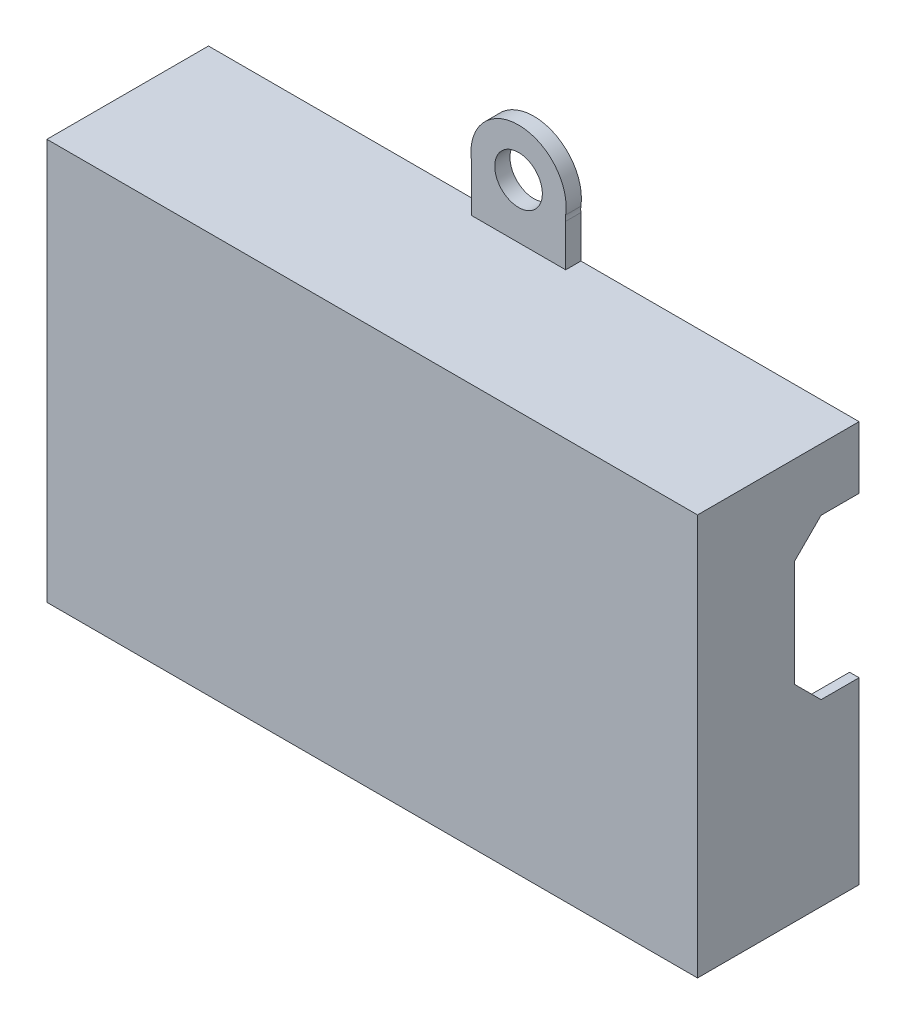
SolidWorks part; units mm, degrees
ref_plane "Front Plane" through (0, 0, 0) normal (0, 0, 1) x (1, 0, 0)
ref_plane "Top Plane" through (0, 0, 0) normal (0, 1, 0) x (1, 0, 0)
ref_plane "Right Plane" through (0, 0, 0) normal (1, 0, 0) x (0, 0, -1)
sketch "Sketch1" plane through (0, 0, 0) normal (0, 0, 1) x (1, 0, 0)
  line L0 (-16.375, 9.825) -> (16.375, -9.825) construction
  line L1 (-16.375, -9.825) -> (-16.575, -9.825) construction
  line L2 (16.575, 10.025) -> (-16.575, 10.025)
  line L3 (16.575, 10.025) -> (16.575, -10.025)
  line L4 (-16.375, 9.825) -> (-16.375, -9.825)
  line L5 (-16.375, -9.825) -> (16.375, -9.825)
  line L6 (16.375, -9.825) -> (16.375, 9.825)
  line L7 (16.375, 9.825) -> (-16.375, 9.825)
  line L8 (-16.375, 9.825) -> (-16.375, -9.825)
  line L9 (-16.375, -9.825) -> (16.375, -9.825)
  line L10 (16.375, -9.825) -> (16.375, 9.825)
  line L11 (16.375, 9.825) -> (-16.375, 9.825)
  line L12 (16.575, -10.025) -> (-16.575, -10.025)
  line L13 (-16.575, 10.025) -> (-16.575, -10.025)
  line L14 (16.575, 10.025) -> (-16.575, -10.025) construction
  line L15 (-13.9701, -11.875) -> (-3.4641, -11.875)
  line L18 (3.4641, -11.875) -> (13.9701, -11.875)
  line L19 (14.8161, -12.3418) -> (24.6724, -27.981)
  line L20 (31.4404, -23.7156) -> (19.404, -4.6171)
  line L21 (19.25, -4.084) -> (19.25, 4.084)
  line L22 (19.404, 4.6171) -> (31.4404, 23.7156)
  line L23 (24.6724, 27.981) -> (14.8161, 12.3418)
  line L24 (13.9701, 11.875) -> (3.4641, 11.875)
  line L25 (-3.4641, 11.875) -> (-13.9701, 11.875)
  line L26 (-14.8161, 12.3418) -> (-24.6724, 27.981)
  line L27 (-31.4404, 23.7156) -> (-19.404, 4.6171)
  line L28 (-19.25, 4.084) -> (-19.25, 3.4641)
  line L29 (-19.25, -3.4641) -> (-19.25, -4.084)
  line L30 (-19.404, -4.6171) -> (-31.4404, -23.7156)
  line L31 (-24.6724, -27.981) -> (-14.8161, -12.3418)
  line L32 (-13.9701, -11.875) -> (-3.4641, -11.875)
  line L33 (3.4641, -11.875) -> (13.9701, -11.875)
  line L34 (14.8161, -12.3418) -> (24.6724, -27.981)
  line L35 (31.4404, -23.7156) -> (19.404, -4.6171)
  line L36 (19.25, -4.084) -> (19.25, 4.084)
  line L37 (19.404, 4.6171) -> (31.4404, 23.7156)
  line L38 (24.6724, 27.981) -> (14.8161, 12.3418)
  line L39 (13.9701, 11.875) -> (3.4641, 11.875)
  line L40 (-3.4641, 11.875) -> (-13.9701, 11.875)
  line L41 (-14.8161, 12.3418) -> (-24.6724, 27.981)
  line L42 (-31.4404, 23.7156) -> (-19.404, 4.6171)
  line L43 (-19.25, 4.084) -> (-19.25, 3.4641)
  line L44 (-19.25, -3.4641) -> (-19.25, -4.084)
  line L45 (-19.404, -4.6171) -> (-31.4404, -23.7156)
  line L46 (-24.6724, -27.981) -> (-14.8161, -12.3418)
  line L47 (16.575, -10.025) -> (-16.575, 10.025) construction
  line L48 (-16.375, -9.825) -> (-16.375, -10.025) construction
  line L49 (-16.575, -10.025) -> (-17.075, -10.025) construction
  line L50 (17.075, 10.525) -> (-17.075, 10.525)
  line L51 (17.075, 10.525) -> (17.075, -10.525)
  line L52 (17.075, -10.525) -> (-17.075, -10.525)
  line L53 (-17.075, 10.525) -> (-17.075, -10.525)
  line L54 (17.075, 10.525) -> (-17.075, -10.525) construction
  line L55 (17.075, -10.525) -> (-17.075, 10.525) construction
  line L56 (-16.575, -10.025) -> (-16.575, -10.525) construction
  line L57 (-20.3929, -2.4744) -> (-17.075, -2.4744)
  line L58 (-20.3929, 2.4744) -> (-17.075, 2.4744)
  line L59 (-2.4744, -13.0179) -> (-2.4744, -10.525)
  line L60 (2.4744, -13.0179) -> (2.4744, -10.525)
  line L61 (-2.4744, 13.0179) -> (-2.4744, 10.525)
  line L62 (2.4744, 13.0179) -> (2.4744, 10.525)
  circle A0 centre (0, -13.375) radius 1.25
  circle A1 centre (-20.75, 0) radius 1.25
  circle A2 centre (0, 13.375) radius 1.25
  arc A32 (-2.4744, -13.0179) -> (-3.4641, -11.875) centre (-3.4641, -12.875) ccw
  arc A33 (-2.4744, -13.0179) -> (2.4744, -13.0179) centre (0, -13.375) ccw
  arc A34 (3.4641, -11.875) -> (2.4744, -13.0179) centre (3.4641, -12.875) ccw
  arc A35 (14.8161, -12.3418) -> (13.9701, -11.875) centre (13.9701, -12.875) ccw
  arc A36 (24.7505, -28.8963) -> (24.6724, -27.981) centre (23.8264, -28.5142) ccw
  arc A37 (24.7505, -28.8963) -> (32.2325, -24.1809) centre (31.8198, -31.8198) ccw
  arc A38 (31.4404, -23.7156) -> (32.2325, -24.1809) centre (32.2864, -23.1824) ccw
  arc A39 (19.25, -4.084) -> (19.404, -4.6171) centre (20.25, -4.084) ccw
  arc A40 (19.404, 4.6171) -> (19.25, 4.084) centre (20.25, 4.084) ccw
  arc A41 (32.2325, 24.1809) -> (31.4404, 23.7156) centre (32.2864, 23.1824) ccw
  arc A42 (32.2325, 24.1809) -> (24.7505, 28.8963) centre (31.8198, 31.8198) ccw
  arc A43 (24.6724, 27.981) -> (24.7505, 28.8963) centre (23.8264, 28.5142) ccw
  arc A44 (13.9701, 11.875) -> (14.8161, 12.3418) centre (13.9701, 12.875) ccw
  arc A45 (2.4744, 13.0179) -> (3.4641, 11.875) centre (3.4641, 12.875) ccw
  arc A46 (2.4744, 13.0179) -> (-2.4744, 13.0179) centre (0, 13.375) ccw
  arc A47 (-3.4641, 11.875) -> (-2.4744, 13.0179) centre (-3.4641, 12.875) ccw
  arc A48 (-14.8161, 12.3418) -> (-13.9701, 11.875) centre (-13.9701, 12.875) ccw
  arc A49 (-24.7505, 28.8963) -> (-24.6724, 27.981) centre (-23.8264, 28.5142) ccw
  arc A50 (-24.7505, 28.8963) -> (-32.2325, 24.1809) centre (-31.8198, 31.8198) ccw
  arc A51 (-31.4404, 23.7156) -> (-32.2325, 24.1809) centre (-32.2864, 23.1824) ccw
  arc A52 (-19.25, 4.084) -> (-19.404, 4.6171) centre (-20.25, 4.084) ccw
  arc A53 (-20.3929, 2.4744) -> (-19.25, 3.4641) centre (-20.25, 3.4641) ccw
  arc A54 (-20.3929, 2.4744) -> (-20.3929, -2.4744) centre (-20.75, 0) ccw
  arc A55 (-19.25, -3.4641) -> (-20.3929, -2.4744) centre (-20.25, -3.4641) ccw
  arc A56 (-19.404, -4.6171) -> (-19.25, -4.084) centre (-20.25, -4.084) ccw
  arc A57 (-32.2325, -24.1809) -> (-31.4404, -23.7156) centre (-32.2864, -23.1824) ccw
  arc A58 (-32.2325, -24.1809) -> (-24.7505, -28.8963) centre (-31.8198, -31.8198) ccw
  arc A59 (-24.6724, -27.981) -> (-24.7505, -28.8963) centre (-23.8264, -28.5142) ccw
  arc A60 (-13.9701, -11.875) -> (-14.8161, -12.3418) centre (-13.9701, -12.875) ccw
  arc A61 (-2.4744, -13.0179) -> (-3.4641, -11.875) centre (-3.4641, -12.875) ccw
  arc A62 (-2.4744, -13.0179) -> (2.4744, -13.0179) centre (0, -13.375) ccw
  arc A63 (3.4641, -11.875) -> (2.4744, -13.0179) centre (3.4641, -12.875) ccw
  arc A64 (14.8161, -12.3418) -> (13.9701, -11.875) centre (13.9701, -12.875) ccw
  arc A65 (24.7505, -28.8963) -> (24.6724, -27.981) centre (23.8264, -28.5142) ccw
  arc A66 (24.7505, -28.8963) -> (32.2325, -24.1809) centre (31.8198, -31.8198) ccw
  arc A67 (31.4404, -23.7156) -> (32.2325, -24.1809) centre (32.2864, -23.1824) ccw
  arc A68 (19.25, -4.084) -> (19.404, -4.6171) centre (20.25, -4.084) ccw
  arc A69 (19.404, 4.6171) -> (19.25, 4.084) centre (20.25, 4.084) ccw
  arc A70 (32.2325, 24.1809) -> (31.4404, 23.7156) centre (32.2864, 23.1824) ccw
  arc A71 (32.2325, 24.1809) -> (24.7505, 28.8963) centre (31.8198, 31.8198) ccw
  arc A72 (24.6724, 27.981) -> (24.7505, 28.8963) centre (23.8264, 28.5142) ccw
  arc A73 (13.9701, 11.875) -> (14.8161, 12.3418) centre (13.9701, 12.875) ccw
  arc A74 (2.4744, 13.0179) -> (3.4641, 11.875) centre (3.4641, 12.875) ccw
  arc A75 (2.4744, 13.0179) -> (-2.4744, 13.0179) centre (0, 13.375) ccw
  arc A76 (-3.4641, 11.875) -> (-2.4744, 13.0179) centre (-3.4641, 12.875) ccw
  arc A77 (-14.8161, 12.3418) -> (-13.9701, 11.875) centre (-13.9701, 12.875) ccw
  arc A78 (-24.7505, 28.8963) -> (-24.6724, 27.981) centre (-23.8264, 28.5142) ccw
  arc A79 (-24.7505, 28.8963) -> (-32.2325, 24.1809) centre (-31.8198, 31.8198) ccw
  arc A80 (-31.4404, 23.7156) -> (-32.2325, 24.1809) centre (-32.2864, 23.1824) ccw
  arc A81 (-19.25, 4.084) -> (-19.404, 4.6171) centre (-20.25, 4.084) ccw
  arc A82 (-20.3929, 2.4744) -> (-19.25, 3.4641) centre (-20.25, 3.4641) ccw
  arc A83 (-20.3929, 2.4744) -> (-20.3929, -2.4744) centre (-20.75, 0) ccw
  arc A84 (-19.25, -3.4641) -> (-20.3929, -2.4744) centre (-20.25, -3.4641) ccw
  arc A85 (-19.404, -4.6171) -> (-19.25, -4.084) centre (-20.25, -4.084) ccw
  arc A86 (-32.2325, -24.1809) -> (-31.4404, -23.7156) centre (-32.2864, -23.1824) ccw
  arc A87 (-32.2325, -24.1809) -> (-24.7505, -28.8963) centre (-31.8198, -31.8198) ccw
  arc A88 (-24.6724, -27.981) -> (-24.7505, -28.8963) centre (-23.8264, -28.5142) ccw
  arc A89 (-13.9701, -11.875) -> (-14.8161, -12.3418) centre (-13.9701, -12.875) ccw
  point P6 (0, 0)
  point P25 (0, 0)
  dimension "D4" = 0.5
  dimension "D5" = 2.5
  dimension "D1" = 0
  dimension "D2" = 0
  dimension "D3" = 0.2
extrude "Boss-Extrude1" add sketch "Sketch1" along normal offset from surface (7.98 mm away) 2.5 contours A84 L57 L53 L58 A82 A83 | L50 L53 L52 L51 L13 L2 L3 L12 | A63 L60 L52 L59 A61 A62 | A76 L61 L50 L62 A74 A75 region at (-2.4011, -11.6286, 0) region at (-9.7747, -10.1238, 0) region at (-18.5911, -2.3949, 0) region at (0, 10.5982, 0) offset beyond the face yes
sketch "Sketch2" plane through (0, 0, 7.98) normal (0, 0, 1) x (1, 0, 0)
  line L0 (-2.5, 10.525) -> (2.4744, 10.525)
  line L1 (-17.075, 2.5) -> (-17.075, -2.5)
  line L2 (-2.5, -10.525) -> (2.4744, -10.525)
  line L6 (-20.1071, -2.4744) -> (-17.075, -2.4744)
  line L7 (-20.1071, -2.4744) -> (-17.075, -2.4744)
  line L8 (-17.075, -2.4744) -> (-17.075, -10.525)
  line L9 (-17.075, -2.4744) -> (-17.075, -10.525)
  line L20 (-17.075, -10.525) -> (-2.4744, -10.525)
  line L21 (-17.075, -10.525) -> (-2.4744, -10.525)
  line L22 (-2.4744, -10.525) -> (-2.4744, -12.7321)
  line L23 (-2.4744, -10.525) -> (-2.4744, -12.7321)
  line L24 (2.4744, -12.7321) -> (2.4744, -10.525)
  line L25 (2.4744, -12.7321) -> (2.4744, -10.525)
  line L26 (2.4744, -10.525) -> (17.075, -10.525)
  line L27 (2.4744, -10.525) -> (17.075, -10.525)
  line L28 (17.075, -10.525) -> (17.075, 10.525)
  line L29 (17.075, -10.525) -> (17.075, 10.525)
  line L30 (17.075, 10.525) -> (2.4744, 10.525)
  line L31 (17.075, 10.525) -> (2.4744, 10.525)
  line L32 (2.4744, 10.525) -> (2.4744, 12.7321)
  line L33 (2.4744, 10.525) -> (2.4744, 12.7321)
  line L34 (-2.4744, 12.7321) -> (-2.4744, 10.525)
  line L35 (-2.4744, 12.7321) -> (-2.4744, 10.525)
  line L36 (-2.4744, 10.525) -> (-17.075, 10.525)
  line L37 (-2.4744, 10.525) -> (-17.075, 10.525)
  line L38 (-17.075, 10.525) -> (-17.075, 2.4744)
  line L39 (-17.075, 10.525) -> (-17.075, 2.4744)
  line L40 (-17.075, 2.4744) -> (-20.1071, 2.4744)
  line L41 (-17.075, 2.4744) -> (-20.1071, 2.4744)
  arc A9 (-20.1071, -2.4744) -> (-20.3929, -2.4744) centre (-20.25, -3.4641) ccw
  arc A10 (-20.1071, -2.4744) -> (-20.3929, -2.4744) centre (-20.25, -3.4641) ccw
  arc A11 (-2.4744, -13.0179) -> (-2.4744, -12.7321) centre (-3.4641, -12.875) ccw
  arc A12 (-2.4744, -13.0179) -> (-2.4744, -12.7321) centre (-3.4641, -12.875) ccw
  arc A13 (-2.4744, -13.0179) -> (2.4744, -13.0179) centre (0, -13.375) ccw
  arc A14 (-2.4744, -13.0179) -> (2.4744, -13.0179) centre (0, -13.375) ccw
  arc A15 (2.4744, -12.7321) -> (2.4744, -13.0179) centre (3.4641, -12.875) ccw
  arc A16 (2.4744, -12.7321) -> (2.4744, -13.0179) centre (3.4641, -12.875) ccw
  arc A17 (2.4744, 13.0179) -> (2.4744, 12.7321) centre (3.4641, 12.875) ccw
  arc A18 (2.4744, 13.0179) -> (2.4744, 12.7321) centre (3.4641, 12.875) ccw
  arc A19 (2.4744, 13.0179) -> (-2.4744, 13.0179) centre (0, 13.375) ccw
  arc A20 (2.4744, 13.0179) -> (-2.4744, 13.0179) centre (0, 13.375) ccw
  arc A21 (-2.4744, 12.7321) -> (-2.4744, 13.0179) centre (-3.4641, 12.875) ccw
  arc A22 (-2.4744, 12.7321) -> (-2.4744, 13.0179) centre (-3.4641, 12.875) ccw
  arc A23 (-20.3929, 2.4744) -> (-20.1071, 2.4744) centre (-20.25, 3.4641) ccw
  arc A24 (-20.3929, 2.4744) -> (-20.1071, 2.4744) centre (-20.25, 3.4641) ccw
  arc A25 (-20.3929, 2.4744) -> (-20.3929, -2.4744) centre (-20.75, 0) ccw
  arc A26 (-20.3929, 2.4744) -> (-20.3929, -2.4744) centre (-20.75, 0) ccw
  dimension "D1" = 0
extrude "Cut-Extrude1" cut sketch "Sketch2" against normal offset from surface (7.18 mm away) 0.8 contours L0 | L1 | L2 region at (0, 12.9704, 7.98) region at (-19.9289, 0, 7.98) region at (0, -12.9704, 7.98) up to face at (-5.364, 0, 0)
sketch "Sketch3" plane through (17.075, 0, 0) normal (1, 0, 0) x (0, 0, -1)
  line L0 (0, 10.525) -> (0, -10.525) construction
  line L1 (0, 7.265) -> (-3.395, 7.265)
  line L2 (0, 7.265) -> (0, -1.115)
  line L3 (0, -1.115) -> (-3.395, -1.115)
  line L4 (-3.395, 7.265) -> (-3.395, -1.115)
  line L6 (-1.3, 7.065) -> (-1.3, 7.265) construction
  line L7 (-1.3, -0.915) -> (-1.3, -1.115) construction
  line L8 (-3.195, 5.375) -> (-3.395, 5.375) construction
  dimension "D1" = 0.2
extrude "Cut-Extrude2" cut sketch "Sketch3" against normal up to next
chamfer "Chamfer1" distance 1.4 angle 45 2 edges at (16.825, -1.115, 3.395) (16.825, 7.265, 3.395)
sketch "Sketch4" plane through (0, 0, 7.98) normal (0, 0, 1) x (1, 0, 0)
  line L4 (-17.075, 10.525) -> (-17.075, -10.525)
  line L8 (-17.075, 10.525) -> (-17.075, -10.525)
  line L17 (-17.075, -10.525) -> (17.075, -10.525)
  line L18 (-17.075, -10.525) -> (17.075, -10.525)
  line L25 (17.075, -10.525) -> (17.075, 10.525)
  line L26 (17.075, -10.525) -> (17.075, 10.525)
  line L27 (17.075, 10.525) -> (-17.075, 10.525)
  line L28 (17.075, 10.525) -> (-17.075, 10.525)
  dimension "D1" = 0
extrude "Boss-Extrude2" add sketch "Sketch4" along normal blind 0.5
sketch "Sketch8" plane through (-17.075, 0, 0) normal (-1, 0, 0) x (0, 0, 1)
  line L1 (5.93, 3.385) -> (7.98, 3.385)
  line L2 (5.93, 3.385) -> (5.93, -3.385)
  line L3 (5.93, -3.385) -> (7.98, -3.385)
  line L4 (7.98, 3.385) -> (7.98, -3.385)
  line L7 (7.08, 3.385) -> (5.93, 3.385) construction
  line L8 (5.93, -3.385) -> (7.08, -3.385) construction
  line L9 (5.93, 3.385) -> (5.93, 2.4) construction
  line L10 (7.98, -3.985) -> (7.98, -2.4) construction
extrude "Cut-Extrude3" cut sketch "Sketch8" against normal up to next
sketch "Sketch9" plane through (0, 0, 7.98) normal (0, 0, -1) x (-1, 0, 0)
  line L1 (16.575, 2.4) -> (17.075, 2.4)
  line L2 (16.575, 2.4) -> (16.575, 3.385)
  line L3 (16.575, 3.385) -> (17.075, 3.385)
  line L4 (17.075, 2.4) -> (17.075, 3.385)
  line L5 (16.575, -2.4) -> (17.075, -2.4)
  line L6 (16.575, -2.4) -> (16.575, -3.385)
  line L7 (16.575, -3.385) -> (17.075, -3.385)
  line L8 (17.075, -2.4) -> (17.075, -3.385)
extrude "Boss-Extrude6" add sketch "Sketch9" along normal blind 0.8
sketch "Sketch5" plane through (0, 0, 0.8) normal (0, 0, 1) x (1, 0, 0)
  line L0 (-2, -13.375) -> (-2, -11.0315)
  line L1 (-17.075, 0) -> (17.075, 0) construction
  line L2 (17.075, -10.525) -> (17.075, 10.525) construction
  line L3 (-2.4744, 11.0315) -> (2.4744, 11.0315)
  line L4 (-2, 13.375) -> (-2, 11.0315)
  line L5 (1.9679, 13.0179) -> (1.9679, 11.0315)
  line L6 (-17.5815, 2.4744) -> (-17.5815, -2.4744)
  line L7 (-17.075, 0) -> (-17.5815, 0) construction
  line L8 (-20.75, 2) -> (-17.5815, 2)
  line L9 (-2.4744, 12.7321) -> (-2.4744, 10.525) construction
  line L10 (-2.4744, 10.525) -> (2.4744, 10.525) construction
  line L11 (2.4744, 10.525) -> (2.4744, 12.7321) construction
  line L12 (-20.1071, -2.4744) -> (-17.075, -2.4744) construction
  line L13 (-17.075, -2.4744) -> (-17.075, 2.4744) construction
  line L14 (-17.075, 2.4744) -> (-20.1071, 2.4744) construction
  line L15 (2.4744, -12.7321) -> (2.4744, -10.525) construction
  line L16 (2.4744, -10.525) -> (-2.4744, -10.525) construction
  line L17 (-2.4744, -10.525) -> (-2.4744, -12.7321) construction
  line L18 (-2.4744, 12.7321) -> (-2.4744, 10.525)
  line L19 (-2.4744, 10.525) -> (2.4744, 10.525)
  line L20 (2.4744, 10.525) -> (2.4744, 12.7321)
  line L21 (-20.1071, -2.4744) -> (-17.075, -2.4744)
  line L22 (-20.75, -2) -> (-17.5815, -2)
  line L23 (-17.075, -2.4744) -> (-17.075, 2.4744)
  line L24 (-17.075, 2.4744) -> (-20.1071, 2.4744)
  line L25 (2.4744, -12.7321) -> (2.4744, -10.525)
  line L26 (2.4744, -10.525) -> (-2.4744, -10.525)
  line L27 (-2.4744, -10.525) -> (-2.4744, -12.7321)
  line L28 (-2.4744, -11.0315) -> (2.4744, -11.0315)
  line L29 (0, -11.0315) -> (0, -10.525) construction
  line L30 (2.4744, -13.0179) -> (1.9679, -13.0179) construction
  line L31 (1.9679, -13.0179) -> (1.9679, -11.0315)
  circle A0 centre (0, 13.375) radius 2
  circle A1 centre (-20.75, 0) radius 2
  arc A3 (2.4744, 13.0179) -> (2.4744, 12.7321) centre (3.4641, 12.875) ccw construction
  arc A4 (2.4744, 13.0179) -> (-2.4744, 13.0179) centre (0, 13.375) ccw construction
  arc A5 (-2.4744, 12.7321) -> (-2.4744, 13.0179) centre (-3.4641, 12.875) ccw construction
  arc A6 (-20.3929, 2.4744) -> (-20.1071, 2.4744) centre (-20.25, 3.4641) ccw construction
  arc A7 (-20.3929, 2.4744) -> (-20.3929, -2.4744) centre (-20.75, 0) ccw construction
  arc A8 (-20.1071, -2.4744) -> (-20.3929, -2.4744) centre (-20.25, -3.4641) ccw construction
  arc A9 (-2.4744, -13.0179) -> (-2.4744, -12.7321) centre (-3.4641, -12.875) ccw construction
  arc A10 (-2.4744, -13.0179) -> (2.4744, -13.0179) centre (0, -13.375) ccw construction
  arc A11 (2.4744, -12.7321) -> (2.4744, -13.0179) centre (3.4641, -12.875) ccw construction
  arc A12 (2.4744, 13.0179) -> (2.4744, 12.7321) centre (3.4641, 12.875) ccw
  arc A13 (2.4744, 13.0179) -> (-2.4744, 13.0179) centre (0, 13.375) ccw
  arc A14 (-2.4744, 12.7321) -> (-2.4744, 13.0179) centre (-3.4641, 12.875) ccw
  arc A15 (-20.3929, 2.4744) -> (-20.1071, 2.4744) centre (-20.25, 3.4641) ccw
  arc A16 (-20.3929, 2.4744) -> (-20.3929, -2.4744) centre (-20.75, 0) ccw
  arc A17 (-20.1071, -2.4744) -> (-20.3929, -2.4744) centre (-20.25, -3.4641) ccw
  arc A18 (-2.4744, -13.0179) -> (-2.4744, -12.7321) centre (-3.4641, -12.875) ccw
  arc A19 (-2.4744, -13.0179) -> (2.4744, -13.0179) centre (0, -13.375) ccw
  arc A20 (2.4744, -12.7321) -> (2.4744, -13.0179) centre (3.4641, -12.875) ccw
  circle A21 centre (0, -13.375) radius 2
  dimension "D1" = 0.5
extrude "Boss-Extrude3" [suppressed] add sketch "Sketch5" along normal up to surface (7.68 mm away) up to face at (0, 0, 8.48)
sketch "Sketch11" plane through (0, 0, 7.98) normal (0, 0, -1) x (-1, 0, 0)
  line L24 (16.675, -4.085) -> (16.675, -2.3)
  line L25 (16.675, -2.3) -> (15.385, -2.3)
  line L26 (15.385, -2.3) -> (15.385, 2.3)
  line L27 (15.385, 2.3) -> (16.675, 2.3)
  line L28 (16.675, 2.3) -> (16.675, 4.085)
  line L29 (16.675, 4.085) -> (10.255, 4.085)
  line L30 (10.255, 4.085) -> (10.255, 2.4)
  line L31 (10.255, 2.4) -> (5.655, 2.4)
  line L32 (5.655, 2.4) -> (5.655, -2.4)
  line L33 (5.655, -2.4) -> (10.255, -2.4)
  line L34 (10.255, -2.4) -> (10.255, -4.085)
  line L35 (10.255, -4.085) -> (16.675, -4.085)
  line L36 (16.675, -4.085) -> (16.675, -2.3)
  line L37 (16.675, -2.3) -> (15.385, -2.3)
  line L38 (15.385, -2.3) -> (15.385, 2.3)
  line L39 (15.385, 2.3) -> (16.675, 2.3)
  line L40 (16.675, 2.3) -> (16.675, 4.085)
  line L41 (16.675, 4.085) -> (10.255, 4.085)
  line L42 (10.255, 4.085) -> (10.255, 2.4)
  line L43 (10.255, 2.4) -> (5.655, 2.4)
  line L44 (5.655, 2.4) -> (5.655, -2.4)
  line L45 (5.655, -2.4) -> (10.255, -2.4)
  line L46 (10.255, -2.4) -> (10.255, -4.085)
  line L47 (10.255, -4.085) -> (16.675, -4.085)
  line L48 (5.655, 1.9) -> (3.655, 1.9)
  line L49 (3.655, 0) -> (17.385, 0) construction
  line L50 (5.655, -1.9) -> (3.655, -1.9)
  line L51 (16.575, 6.085) -> (16.575, 4.085)
  line L53 (16.575, 10.025) -> (16.575, 2.4) construction
  line L54 (16.575, -6.085) -> (16.575, -4.085)
  line L55 (16.575, -2.4) -> (16.575, -10.025) construction
  line L60 (18.675, -6.085) -> (18.675, -0.3)
  line L61 (18.675, -0.3) -> (17.385, -0.3)
  line L62 (17.385, -0.3) -> (17.385, 0.3)
  line L63 (17.385, 0.3) -> (18.675, 0.3)
  line L64 (18.675, 0.3) -> (18.675, 6.085)
  line L65 (18.675, 6.085) -> (8.255, 6.085)
  line L66 (8.255, 6.085) -> (8.255, 4.4)
  line L67 (8.255, 4.4) -> (3.655, 4.4)
  line L68 (3.655, 4.4) -> (3.655, -4.4)
  line L69 (3.655, -4.4) -> (8.255, -4.4)
  line L70 (8.255, -4.4) -> (8.255, -6.085)
  line L71 (8.255, -6.085) -> (18.675, -6.085)
  line L72 (18.675, -6.085) -> (18.675, -0.3)
  line L73 (18.675, -0.3) -> (17.385, -0.3)
  line L74 (17.385, -0.3) -> (17.385, 0.3)
  line L75 (17.385, 0.3) -> (18.675, 0.3)
  line L76 (18.675, 0.3) -> (18.675, 6.085)
  line L77 (18.675, 6.085) -> (8.255, 6.085)
  line L78 (8.255, 6.085) -> (8.255, 4.4)
  line L79 (8.255, 4.4) -> (3.655, 4.4)
  line L80 (3.655, 4.4) -> (3.655, -4.4)
  line L81 (3.655, -4.4) -> (8.255, -4.4)
  line L82 (8.255, -4.4) -> (8.255, -6.085)
  line L83 (8.255, -6.085) -> (18.675, -6.085)
  line M27 (16.575, -10.025) -> (16.575, -2.4)
  line M31 (16.575, 2.4) -> (16.575, 10.025)
  dimension "D3" = 0.5
  dimension "D1" = 0.1
  dimension "D2" = 2.1
extrude "Boss-Extrude7" add sketch "Sketch11" along normal blind 2.5 contours L79 L80 L48 L44 L43 L42 L41 L77 L78 M31 | L82 L83 L47 L46 L45 L44 L50 L80 L81 M27 region at (-9.8383, -4.2692, 7.98) region at (-9.8383, 4.2692, 7.98)
sketch "Sketch12" plane through (0, 0, 7.98) normal (0, 0, -1) x (-1, 0, 0)
  line L0 (16.575, -6.085) -> (16.575, -10.025) construction
  line L1 (-3.0335, 0) -> (1.6631, 0) construction
  line L2 (16.575, 8.055) -> (14.605, 8.055)
  line L3 (16.575, 8.055) -> (16.575, 6.085)
  line L4 (16.575, 6.085) -> (14.605, 6.085)
  line L5 (16.575, -8.055) -> (14.605, -8.055)
  line L6 (16.575, -8.055) -> (16.575, -6.085)
  line L7 (16.575, -6.085) -> (14.605, -6.085)
  line L8 (14.605, -8.055) -> (14.605, -6.085)
  line L9 (8.255, -6.085) -> (16.575, -6.085) construction
  line L10 (14.605, 8.055) -> (14.605, 6.085)
  line L11 (-16.575, 10.025) -> (-16.575, -10.025) construction
  line L12 (-14.605, 2) -> (-16.575, 2)
  line L13 (-14.605, 2) -> (-14.605, -2)
  line L14 (-14.605, -2) -> (-16.575, -2)
  line L15 (-16.575, 2) -> (-16.575, -2)
  line L16 (-14.605, 2) -> (-16.575, -2) construction
  line L17 (-14.605, -2) -> (-16.575, 2) construction
  point P16 (-15.59, 0)
  dimension "D1" = 4
extrude "Boss-Extrude8" add sketch "Sketch12" along normal up to surface (3.95 mm away)
sketch "Sketch13" plane through (-17.075, 0, 0) normal (-1, 0, 0) x (0, 0, 1)
  line L0 (7.18, 2.4) -> (7.18, 3.385) construction
  line L1 (7.98, 2.4) -> (7.18, 2.4)
  line L2 (7.98, 2.4) -> (7.98, 2.9)
  line L3 (7.98, 2.9) -> (7.18, 2.9)
  line L4 (7.18, 2.4) -> (7.18, 2.9)
  line L5 (5.93, 0) -> (7.98, 0) construction
  line L6 (7.18, 3.385) -> (5.43, 3.385)
  line L7 (7.18, 3.385) -> (7.18, 3.885)
  line L8 (7.18, 3.885) -> (5.43, 3.885)
  line L9 (5.43, 3.385) -> (5.43, 3.885)
  line L10 (5.93, 3.385) -> (5.93, -3.385) construction
  line L11 (7.98, -2) -> (7.98, 2) construction
  line L12 (5.43, 1.6925) -> (5.93, 1.6925) construction
  line L13 (5.43, 3.385) -> (5.93, 3.385)
  line L14 (5.43, 3.385) -> (5.43, -3.385)
  line L15 (5.93, 0) -> (5.93, -3.385)
  line L16 (5.93, 3.385) -> (5.93, 0)
  line L17 (7.98, -2.4) -> (7.98, -2.9)
  line L18 (7.98, -2.9) -> (7.18, -2.9)
  line L19 (7.18, -3.385) -> (7.18, -3.885)
  line L20 (7.18, -3.885) -> (5.43, -3.885)
  line L21 (5.43, -3.385) -> (5.43, -3.885)
  line L22 (5.43, 3.385) -> (5.43, -3.385)
  line M12 (7.98, -2.4) -> (7.18, -2.4)
  line M13 (7.18, -2.4) -> (7.18, -3.385)
  line M14 (7.18, -3.385) -> (5.93, -3.385)
  line M15 (5.93, -3.385) -> (5.93, 3.385)
  line M16 (5.93, 3.385) -> (7.18, 3.385)
  line M17 (7.18, 3.385) -> (7.18, 2.4)
  line M18 (7.18, 2.4) -> (7.98, 2.4)
  dimension "D1" = 0.5
extrude "Cut-Extrude4" cut sketch "Sketch13" against normal up to next contours L9 L6 L7 L8 M16 | L2 L3 M17 M18 | L14 L21 L20 L19 L6 M14 M15 | L18 L17 M12 M13 region at (-17.075, -2.65, 7.58) region at (-17.075, 3.635, 6.305) region at (-17.075, 2.65, 7.58) region at (-17.075, -0.7466, 5.8084)
